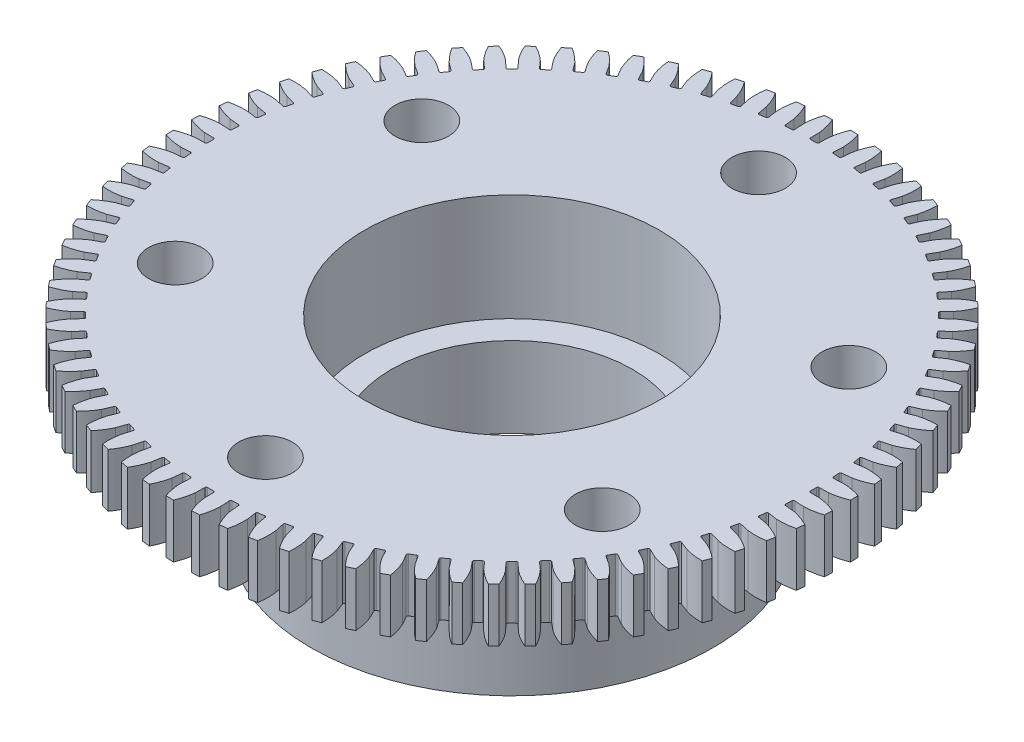
SolidWorks part; units mm, degrees
material "Brass"
ref_plane "Plano frontal" through (0, 0, 0) normal (0, 0, 1) x (1, 0, 0)
ref_plane "Plano superior" through (0, 0, 0) normal (0, 1, 0) x (1, 0, 0)
ref_plane "Plano direito" through (0, 0, 0) normal (1, 0, 0) x (0, 0, -1)
sketch "Sketch1" plane through (0, 0, 0) normal (0, 1, 0) x (1, 0, 0)
  circle A0 centre (0, 0) radius 12.3
  circle A1 centre (0, 0) radius 4.5
  circle A2 centre (0, 9.2) radius 1
  circle A3 centre (7.9674, 4.6) radius 1
  circle A4 centre (7.9674, -4.6) radius 1
  circle A5 centre (0, -9.2) radius 1
  circle A6 centre (-7.9674, -4.6) radius 1
  circle A7 centre (-7.9674, 4.6) radius 1
  dimension "D1" = 24.6
  dimension "D2" = 9
  dimension "D4" = 2
  dimension "D3" = 9.2
  dimension "D6" = 9.2
  dimension "D5" = 6
extrude "Boss-Extrude1" add sketch "Sketch1" along normal blind 2
sketch "Sketch2" plane through (0, 2, 0) normal (0, 1, 0) x (1, 0, 0)
  line L0 (0, 0) -> (0, 11.25) construction
  line L1 (0, 0) -> (0.2356, 11.9977) construction
  line L2 (0.1682, 11.6488) -> (0.1613, 11.2985)
  line L3 (-0.1682, 11.6488) -> (-0.1613, 11.2985)
  circle A0 centre (0, 0) radius 12.3 construction
  circle A1 centre (0, 0) radius 12.3
  circle A2 centre (0, 0) radius 12 construction
  circle A3 centre (0, 0) radius 11.65 construction
  arc A4 (0.1109, 11.2495) -> (-0.1109, 11.2495) centre (0, 0) ccw
  arc A5 (0.3394, 12.2953) -> (0.2356, 11.9977) centre (2.4692, 11.3853) ccw
  arc A6 (0.2356, 11.9977) -> (0.1682, 11.6488) centre (2.4692, 11.3853) ccw
  arc A7 (-0.2356, 11.9977) -> (-0.1682, 11.6488) centre (-2.4692, 11.3853) cw
  arc A8 (-0.3394, 12.2953) -> (-0.2356, 11.9977) centre (-2.4692, 11.3853) cw
  arc A9 (0.1613, 11.2985) -> (0.1109, 11.2495) centre (0.1113, 11.2995) cw
  arc A10 (-0.1613, 11.2985) -> (-0.1109, 11.2495) centre (-0.1113, 11.2995) ccw
  point P20 (0.1604, 11.2489)
  point P23 (-0.1604, 11.2489)
  circle M7 centre (0, 0) radius 12.3
  dimension "D1" = 24
  dimension "D2" = 23.3
  dimension "D3" = 22.5
  dimension "D5" = 0.05
  dimension "D6" = 2.316
  dimension "D4" = 1.125
  dimension "D7" = 1.125
extrude "Cut-Extrude1" cut sketch "Sketch2" against normal up to surface (2 mm away) contours L3 A10 A4 A9 L2 A6 A5 A8 A7 M7 region at (0, 2, -11.8466) up to face at (0, 0, 12.3)
pattern_circular "CirPattern1" count 80 every 4.5 about axis through (0, 2, 0) along (0, 1, 0) of "Cut-Extrude1"
sketch "Sketch3" plane through (0, 0, 0) normal (0, -1, 0) x (1, 0, 0)
  circle A0 centre (0, 0) radius 7.5
  circle A1 centre (0, 0) radius 4.5
  circle A2 centre (0, 0) radius 4.5 construction
  dimension "D1" = 15
extrude "Boss-Extrude2" add sketch "Sketch3" along normal blind 5
sketch "Sketch4" plane through (0, -5, 0) normal (0, -1, 0) x (1, 0, 0)
  circle A0 centre (0, 0) radius 5.5
  dimension "D1" = 11
extrude "Cut-Extrude2" cut sketch "Sketch4" along normal blind 4 from surface starting at face at (0, 2, 0)
